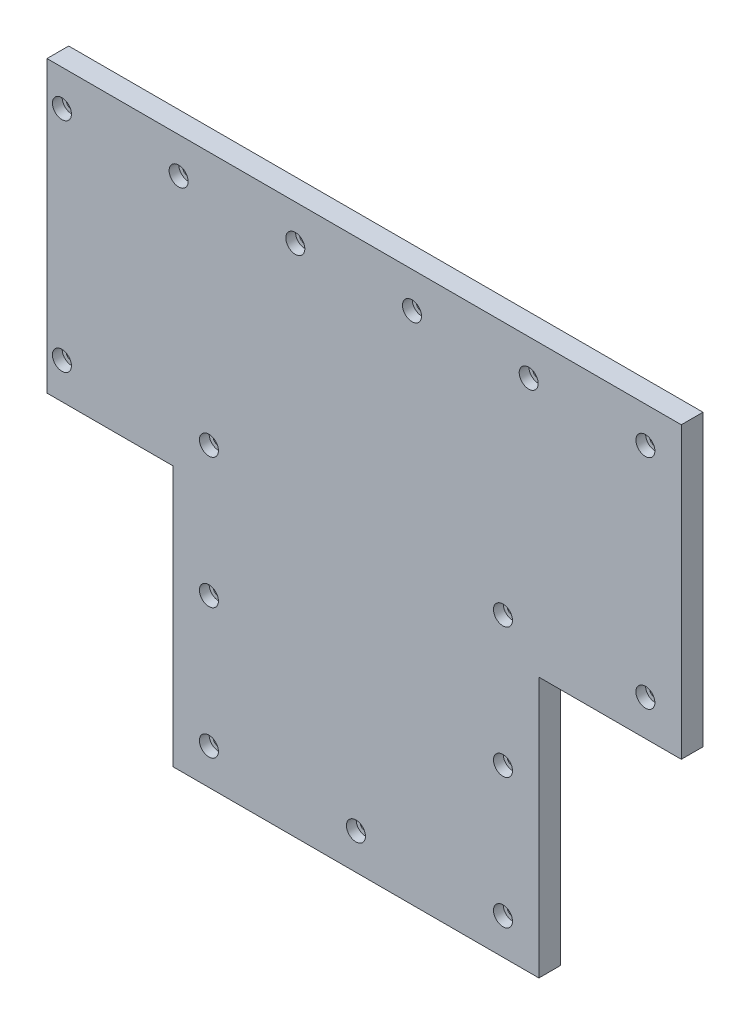
SolidWorks part; units mm, degrees
ref_plane "Front Plane" through (0, 0, 0) normal (0, 0, 1) x (1, 0, 0)
ref_plane "Top Plane" through (0, 0, 0) normal (0, 1, 0) x (1, 0, 0)
ref_plane "Right Plane" through (0, 0, 0) normal (1, 0, 0) x (0, 0, -1)
sketch "Outline" plane through (0, 0, 0) normal (0, 0, 1) x (1, 0, 0)
  line L0 (78.4332, -3.5355) -> (81.9688, 0)
  line L1 (0, 0) -> (180, 0)
  line L2 (0, 0) -> (0, -53.7401)
  line L3 (0, -53.7401) -> (180, -53.7401)
  line L4 (180, 0) -> (180, -53.7401)
  line L9 (81.9688, 0) -> (132.1734, -50.2046)
  line L10 (132.1734, -50.2046) -> (128.6378, -53.7401)
  line L11 (128.6378, -53.7401) -> (78.4332, -3.5355)
  line L12 (72.0693, 0) -> (68.5337, -3.5355)
  line L13 (68.5337, -3.5355) -> (118.7383, -53.7401)
  line L14 (118.7383, -53.7401) -> (122.2739, -50.2046)
  line L15 (122.2739, -50.2046) -> (72.0693, 0)
  line L16 (0, 10.6299) -> (0, -64.3701) construction
  line L17 (73.4835, -0.7071) -> (126.5165, -53.7401) construction
  line L18 (126.5165, -53.7401) -> (127.2236, -53.033) construction
  line L19 (127.2236, -53.033) -> (74.1906, 0) construction
  line L20 (74.1906, 0) -> (73.4835, -0.7071) construction
  line L21 (78.0797, -3.8891) -> (78.4332, -3.5355) construction
  line L22 (77.3726, -4.5962) -> (77.019, -4.9497) construction
  line L23 (100, -27.2236) -> (100, -53.7401) construction
  line L24 (62.3536, -53.7401) -> (138.3536, -53.7401)
  line L25 (62.3536, -53.7401) -> (62.3536, -129.9401)
  line L26 (62.3536, -129.9401) -> (138.3536, -129.9401)
  line L27 (138.3536, -53.7401) -> (138.3536, -129.9401)
  line L28 (62.3536, -53.7401) -> (74.1906, -53.7401)
  line L29 (62.3536, -53.7401) -> (62.3536, -55.7401)
  line L30 (62.3536, -55.7401) -> (74.1906, -55.7401)
  line L31 (74.1906, -53.7401) -> (74.1906, -55.7401)
  line L32 (138.3536, -53.7401) -> (126.5165, -53.7401)
  line L33 (138.3536, -53.7401) -> (138.3536, -55.7401)
  line L34 (138.3536, -55.7401) -> (126.5165, -55.7401)
  line L35 (126.5165, -53.7401) -> (126.5165, -55.7401)
  line L36 (62.3536, -57.9901) -> (74.1906, -57.9901)
  line L37 (62.3536, -57.9901) -> (62.3536, -59.9901)
  line L38 (62.3536, -59.9901) -> (74.1906, -59.9901)
  line L39 (74.1906, -57.9901) -> (74.1906, -59.9901)
  line L40 (138.3536, -57.9901) -> (126.5165, -57.9901)
  line L41 (138.3536, -57.9901) -> (138.3536, -59.9901)
  line L42 (138.3536, -59.9901) -> (126.5165, -59.9901)
  line L43 (126.5165, -57.9901) -> (126.5165, -59.9901)
  line L48 (137.8536, -55.7401) -> (137.8536, -56.2401) construction
  line L49 (62.8536, -56.2401) -> (137.8536, -56.2401) construction
  line L50 (62.8536, -56.2401) -> (62.8536, -57.4901) construction
  line L51 (62.8536, -57.4901) -> (137.8536, -57.4901) construction
  line L52 (137.8536, -56.2401) -> (137.8536, -57.4901) construction
  line L53 (137.8536, -57.4901) -> (137.8536, -57.9901) construction
  line L54 (137.8536, -56.2401) -> (138.3536, -56.2401) construction
  line L55 (62.8536, -56.2401) -> (62.3536, -56.2401) construction
  line L56 (0, 23.1299) -> (0, -76.8701) construction
  line L57 (10, 10) -> (190, 10)
  line L58 (0, 28.1299) -> (10, 28.1299)
  line L59 (0, 28.1299) -> (0, 0)
  line L60 (0, 0) -> (10, 0)
  line L61 (10, 28.1299) -> (10, 0)
  line L62 (0, -53.7401) -> (10, -53.7401)
  line L63 (0, -53.7401) -> (0, -81.8701)
  line L64 (0, -81.8701) -> (10, -81.8701)
  line L65 (10, -53.7401) -> (10, -81.8701)
  line L66 (190, 10) -> (190, -63.7401)
  line L67 (190, -63.7401) -> (148.3536, -63.7401)
  line L68 (148.3536, -63.7401) -> (148.3536, -139.9401)
  line L69 (148.3536, -139.9401) -> (52.3536, -139.9401)
  line L70 (52.3536, -139.9401) -> (52.3536, -63.7401)
  line L71 (52.3536, -63.7401) -> (10, -63.7401)
  line L72 (180, 0) -> (180, 10) construction
  line L73 (180, 0) -> (190, 0) construction
  line L74 (148.3536, -63.7401) -> (148.3536, -53.7401) construction
  line L75 (138.3536, -129.9401) -> (148.3536, -129.9401) construction
  line L76 (62.3536, -129.9401) -> (62.3536, -139.9401) construction
  line L77 (62.3536, -129.9401) -> (52.3536, -129.9401) construction
  line L78 (52.3536, -63.7401) -> (52.3536, -53.7401) construction
  line L79 (68.5337, -3.5355) -> (68.5337, 0)
  line L80 (126.5165, -53.7401) -> (127.5772, -52.6795)
  line L81 (10, 0) -> (10, -53.7401)
  line L82 (10, 5) -> (190, 5) construction
  line L83 (185, 10) -> (185, -63.7401) construction
  line L84 (190, -58.7401) -> (138.3536, -58.7401) construction
  line L85 (10, -58.7401) -> (62.3536, -58.7401) construction
  line L86 (57.3536, -53.7401) -> (57.3536, -139.9401) construction
  line L87 (52.3536, -134.9401) -> (148.3536, -134.9401) construction
  line L88 (143.3536, -53.7401) -> (143.3536, -139.9401) construction
  line L89 (10, 10) -> (0, 10)
  line L90 (190, -11.6201) -> (200, -11.6201) construction
  line L91 (190, -11.6201) -> (190, -42.1201) construction
  line L92 (190, -42.1201) -> (200, -42.1201) construction
  line L93 (200, -11.6201) -> (200, -42.1201) construction
  line L94 (10, -63.7401) -> (0, -63.7401)
  point P18 (0, -26.8701)
  point P51 (0, -26.8701)
  point P52 (0, -26.8701)
  point P80 (180, 5)
  point P83 (185, 0)
  point P85 (200, -26.8701)
  point P86 (190, -26.8701)
  point P94 (148.3536, -58.7401)
  point P103 (57.3536, -129.9401)
  point P104 (143.3536, -129.9401)
  point P105 (62.3536, -134.9401)
  dimension "D23" = 10
  dimension "D24" = 30.5
  dimension "D1" = 5
  dimension "D2" = 45
  dimension "D3" = 1
  dimension "D4" = 75
  dimension "D5" = 200
  dimension "D6" = 53.7401
  dimension "D7" = 0.5
  dimension "D8" = 75
  dimension "D9" = 1.25
  dimension "D10" = 0.5
  dimension "D11" = 76
  dimension "D12" = 52.3259
  dimension "D13" = 0.5
  dimension "D14" = 2
  dimension "D15" = 100
  dimension "D16" = 76.2
  dimension "D17" = 75
  dimension "D18" = 100
  dimension "D19" = 10
  dimension "D20" = 5
  dimension "D21" = 10
  dimension "D22" = 18.1299
sketch "Hole Locations" plane through (0, 0, 0) normal (0, 0, 1) x (1, 0, 0)
  line L8 (10, 5) -> (190, 5) construction
  line L9 (10, 28.1299) -> (10, 0) construction
  line L10 (10, -58.7401) -> (62.3536, -58.7401) construction
  line L11 (57.3536, -53.7401) -> (57.3536, -139.9401) construction
  line L12 (143.3536, -53.7401) -> (143.3536, -139.9401) construction
  line L13 (52.3536, -134.9401) -> (148.3536, -134.9401) construction
  line L14 (190, -58.7401) -> (138.3536, -58.7401) construction
  line L15 (185, 10) -> (185, -63.7401) construction
  circle A0 centre (14.3688, 5) radius 1.9431
  circle A1 centre (14.3688, 5) radius 4.3688 construction
  circle A2 centre (48.495, 5) radius 1.9431
  circle A3 centre (48.495, 5) radius 4.3688 construction
  circle A4 centre (82.6213, 5) radius 1.9431
  circle A5 centre (82.6213, 5) radius 4.3688 construction
  circle A6 centre (116.7475, 5) radius 1.9431
  circle A7 centre (116.7475, 5) radius 4.3688 construction
  circle A8 centre (150.8738, 5) radius 1.9431
  circle A9 centre (150.8738, 5) radius 4.3688 construction
  circle A10 centre (185, 5) radius 1.9431
  circle A11 centre (185, 5) radius 4.3688 construction
  circle A12 centre (14.3688, -58.7401) radius 1.9431
  circle A13 centre (14.3688, -58.7401) radius 4.3688 construction
  circle A14 centre (57.3536, -58.7401) radius 1.9431
  circle A15 centre (57.3536, -58.7401) radius 4.3688 construction
  circle A16 centre (185, -58.7401) radius 1.9431
  circle A17 centre (185, -58.7401) radius 4.3688 construction
  circle A18 centre (143.3536, -58.7401) radius 1.9431
  circle A19 centre (143.3536, -58.7401) radius 4.3688 construction
  circle A20 centre (57.3536, -134.9401) radius 1.9431
  circle A21 centre (57.3536, -134.9401) radius 4.3688 construction
  circle A22 centre (143.3536, -134.9401) radius 1.9431
  circle A23 centre (143.3536, -134.9401) radius 4.3688 construction
  circle A24 centre (57.3536, -96.8401) radius 1.9431
  circle A25 centre (57.3536, -96.8401) radius 4.3688 construction
  circle A26 centre (143.3536, -96.8401) radius 1.9431
  circle A27 centre (143.3536, -96.8401) radius 4.3688 construction
  circle A28 centre (100.3536, -134.9401) radius 1.9431
  circle A29 centre (100.3536, -134.9401) radius 4.3688 construction
  point P5 (15.9366, 5)
  point P25 (15.8274, -58.7401)
  point P27 (14.3688, -71.4228)
  point P31 (54.1459, -58.7401)
  point P35 (206.7106, -60.7454)
  point P39 (143.3536, -58.7401)
  point P42 (57.3536, -58.7401)
  point P43 (49.9418, -58.7401)
  point P44 (143.3536, -58.7401)
  point P45 (185, -58.7401)
  point P48 (57.9105, -58.7401)
  point P49 (0, 0)
  point P50 (0, 0)
  point P51 (22.1879, -58.7401)
  point P55 (42.4662, -130.2988)
  point P59 (162.7145, -130.2988)
  point P66 (158.6209, -94.4802)
  point P67 (33.7673, -90.6425)
  point P68 (57.3536, -134.9401)
  point P69 (0, 0)
  point P71 (143.3536, -134.9401)
  point P72 (0, 0)
  point P76 (0, 0)
  point P77 (100.3536, -134.9401)
  point P79 (57.3536, -134.9401)
  point P82 (143.3536, -134.9401)
  point P83 (0, 0)
  point P84 (0, 0)
  point P85 (0, 0)
  point P88 (185, -58.7401)
  point P91 (0, 0)
  point P92 (0, 0)
  point P93 (0, 0)
  point P94 (0, 0)
  point P95 (0, 0)
  point P96 (0, 0)
  point P97 (0, 0)
  point P98 (0, 0)
  dimension "D1" = 3.8862
  dimension "D2" = 8.7376
  dimension "D4" = 34.1262
  dimension "D3" = 6
extrude "Boss-Extrude1" add sketch "Outline" along normal blind 6.35 contours L71 L70 L69 L68 L67 L66 L57 L61 L1 L4 L3 L27 L26 L25 L65 | L43 L40 L27 L34 L35 L3 L24 L31 L30 L25 L36 L39 L38 L26 L42 | L31 L3 L25 L30 | L39 L36 L25 L38 | L24 L35 L34 L27 L3 | L40 L43 L42 L27 | L1 L81 L3 L24 L13 L79 | L3 L80 L11 L0 L1 L15 L14 | L14 L15 L12 L13 | L11 L10 L9 L0 | L9 L10 L3 L4 L1 | L80 L24 L11 | L79 L12 L1 region at (100.1794, -26.7004, 0) region at (105.3033, -26.8701, 0) region at (77.019, 2.3427, 0) region at (142.694, -23.5828, 0) region at (127.5772, -53.3866, 0) region at (69.7123, -1.1785, 0) region at (95.4038, -26.8701, 0) region at (132.435, -54.7401, 0) region at (100.3536, -92.4215, 0) region at (52.4252, -29.7691, 0) region at (68.2721, -54.7401, 0) region at (132.435, -58.9901, 0) region at (68.2721, -58.9901, 0)
hole_wizard "CBORE for #4 Socket Head Cap Screw1" positions "3DSketch1" profile "Sketch7" counterbore size "#4" standard "ANSI Inch" end condition through all
sketch3d "3DSketch1"
  point P0 (14.3688, 5, 6.35)
  point P2 (14.3688, -58.7401, 6.35)
  point P4 (57.3536, -58.7401, 6.35)
  point P6 (48.495, 5, 6.35)
  point P8 (82.6213, 5, 6.35)
  point P10 (116.7475, 5, 6.35)
  point P12 (150.8738, 5, 6.35)
  point P14 (143.3536, -58.7401, 6.35)
  point P16 (143.3536, -96.8401, 6.35)
  point P18 (57.3536, -134.9401, 6.35)
  point P20 (57.3536, -96.8401, 6.35)
  point P22 (185, -58.7401, 6.35)
  point P24 (185, 5, 6.35)
  point P47 (100.3536, -134.9401, 6.35)
  point P51 (143.3536, -134.9401, 6.35)
sketch "Sketch7" plane through (14.3688, 5, 6.35) normal (1, 0, 0) x (0, -1, 0)
  line L0 (0, 0) -> (0, 6.35)
  line L1 (0, 6.35) -> (1.6319, 6.35)
  line L3 (1.6319, 6.35) -> (1.6319, 2.8448)
  line L4 (1.6319, 2.8448) -> (2.7788, 2.8448)
  line L5 (2.7788, 2.8448) -> (2.7788, 0)
  line L7 (2.7788, 0) -> (0, 0)
  line L11 (0, -6.35) -> (0, 107.95) construction
  dimension "Thru Hole Dia." = 3.2639
  dimension "Thru Hole Depth" = 6.35
  dimension "C'Bore Dia." = 5.5575
  dimension "C'Bore Depth" = 2.8448
extrude "Boss-Extrude2" add sketch "Outline<10>" against normal blind 2 contours L11 L10 L9 L0 | L14 L15 L12 L13 region at (105.3033, -26.8701, 0) region at (95.4038, -26.8701, 0)
sketch "Outline<10>" plane through (0, 0, 0) normal (0, 0, 1) x (1, 0, 0) same geometry as "Outline"
sketch "Sketch8" plane through (0, 0, 0) normal (0, 0, 1) x (1, 0, 0)
  line L0 (0, 10) -> (0, 13.5)
  line L1 (0, 13.5) -> (193.5, 13.5)
  line L2 (193.5, 13.5) -> (193.5, -67.2401)
  line L3 (193.5, -67.2401) -> (151.8536, -67.2401)
  line L4 (151.8536, -67.2401) -> (151.8536, -143.4401)
  line L5 (151.8536, -143.4401) -> (48.8536, -143.4401)
  line L6 (48.8536, -143.4401) -> (48.8536, -67.2401)
  line L7 (48.8536, -67.2401) -> (0, -67.2401)
  line L8 (0, -67.2401) -> (0, -63.7401)
  line L9 (190, 10) -> (193.5, 10) construction
  line L10 (190, 10) -> (190, 13.5) construction
  line L11 (190, -63.7401) -> (193.5, -63.7401) construction
  line L12 (190, -63.7401) -> (190, -67.2401) construction
  line L13 (151.8536, -67.2401) -> (151.8536, -63.7401) construction
  line L14 (190, -63.7401) -> (148.3536, -63.7401) construction
  line L15 (151.8536, -67.2401) -> (148.3536, -67.2401) construction
  line L16 (148.3536, -63.7401) -> (148.3536, -139.9401) construction
  line L17 (148.3536, -139.9401) -> (151.8536, -139.9401) construction
  line L18 (148.3536, -139.9401) -> (148.3536, -143.4401) construction
  line L19 (52.3536, -139.9401) -> (52.3536, -143.4401) construction
  line L20 (52.3536, -139.9401) -> (48.8536, -139.9401) construction
  line L21 (48.8536, -67.2401) -> (52.3536, -67.2401) construction
  line L22 (52.3536, -139.9401) -> (52.3536, -63.7401) construction
  line L23 (48.8536, -67.2401) -> (48.8536, -63.7401) construction
  line L25 (0, 13.5) -> (0, 15.5)
  line L26 (0, 15.5) -> (195.5, 15.5)
  line L27 (195.5, 15.5) -> (195.5, -69.2401)
  line L28 (195.5, -69.2401) -> (153.8536, -69.2401)
  line L29 (153.8536, -69.2401) -> (153.8536, -145.4401)
  line L30 (153.8536, -145.4401) -> (46.8536, -145.4401)
  line L31 (46.8536, -145.4401) -> (46.8536, -69.2401)
  line L32 (46.8536, -69.2401) -> (0, -69.2401)
  line L33 (0, -69.2401) -> (0, -67.2401)
  line L34 (46.8536, -69.2401) -> (48.8536, -69.2401) construction
  line L35 (46.8536, -69.2401) -> (46.8536, -67.2401) construction
  line L36 (48.8536, -143.4401) -> (46.8536, -143.4401) construction
  line L37 (48.8536, -143.4401) -> (48.8536, -145.4401) construction
  line L38 (151.8536, -143.4401) -> (153.8536, -143.4401) construction
  line L39 (151.8536, -143.4401) -> (151.8536, -145.4401) construction
  line L40 (153.8536, -69.2401) -> (153.8536, -67.2401) construction
  line L41 (153.8536, -69.2401) -> (151.8536, -69.2401) construction
  line L42 (193.5, -67.2401) -> (195.5, -67.2401) construction
  line L43 (193.5, -67.2401) -> (193.5, -69.2401) construction
  line L44 (193.5, 13.5) -> (195.5, 13.5) construction
  line L45 (193.5, 13.5) -> (193.5, 15.5) construction
  line L46 (0, -63.7401) -> (0, -69.2401)
  line L47 (0, -63.7401) -> (52.3536, -63.7401)
  line L48 (52.3536, -63.7401) -> (52.3536, -139.9401)
  line L49 (52.3536, -139.9401) -> (148.3536, -139.9401)
  line L50 (148.3536, -139.9401) -> (148.3536, -63.7401)
  line L51 (148.3536, -63.7401) -> (190, -63.7401)
  line L52 (190, -63.7401) -> (190, 10)
  line L53 (190, 10) -> (0, 10)
  line L54 (0, 9.5) -> (189.5, 9.5)
  line L56 (189.5, 9.5) -> (189.5, -63.2401)
  line L57 (189.5, -63.2401) -> (147.8536, -63.2401)
  line L58 (147.8536, -63.2401) -> (147.8536, -139.4401)
  line L59 (147.8536, -139.4401) -> (52.8536, -139.4401)
  line L60 (52.8536, -139.4401) -> (52.8536, -63.2401)
  line L61 (52.8536, -63.2401) -> (0, -63.2401)
  line L62 (189.5, 9.5) -> (189.5, 10) construction
  line L63 (189.5, 9.5) -> (190, 9.5) construction
  line L64 (189.5, -63.2401) -> (190, -63.2401) construction
  line L65 (189.5, -63.2401) -> (189.5, -63.7401) construction
  line L66 (148.3536, -63.7401) -> (148.3536, -63.2401) construction
  line L67 (148.3536, -63.7401) -> (147.8536, -63.7401) construction
  line L68 (147.8536, -139.4401) -> (148.3536, -139.4401) construction
  line L69 (147.8536, -139.4401) -> (147.8536, -139.9401) construction
  line L70 (52.8536, -139.4401) -> (52.8536, -139.9401) construction
  line L71 (52.8536, -139.4401) -> (52.3536, -139.4401) construction
  line L72 (52.3536, -63.7401) -> (52.3536, -63.2401) construction
  line L73 (52.3536, -63.7401) -> (52.8536, -63.7401) construction
  line L74 (0, 9.5) -> (0, 10)
  line L75 (0, -63.2401) -> (0, -63.7401)
  line L76 (10, 10) -> (10, 15.5)
  line L77 (10, -63.7401) -> (10, -69.2401)
  line L78 (52.3536, -63.7401) -> (10, -63.7401) construction
  line L79 (10, 10) -> (190, 10) construction
  point P40 (0, 0)
  point P41 (0, 0)
  point P67 (0, 0)
  point P68 (0, 0)
  point P93 (0, 0)
  point P94 (0, 0)
  point P95 (0, 0)
  point P96 (0, 0)
  point P97 (52.8536, -62.5066)
  point P98 (0, 0)
  point P101 (0, 0)
  point P102 (0, 0)
  point P103 (190, 10)
  dimension "D1" = 3.5
  dimension "D2" = 2
  dimension "D3" = 0.5
extrude "Boss-Extrude3" add sketch "Sketch8" along normal up to surface (6.35 mm away) contours L53 L52 L51 L50 L49 L48 L47 L8 L7 L6 L5 L4 L3 L2 L1 L0 | L33 L32 L31 L30 L29 L28 L27 L26 L25 L1 L2 L3 L4 L5 L6 L7 region at (12.4146, 11.75, 0) region at (12.4558, 14.5, 0) up to face at (17.1476, 5, 6.35)
extrude "Cut-Extrude1" cut sketch "Sketch8<5>" along normal blind 3 contours L53 L52 L51 L50 L49 L48 L47 L8 L7 L6 L5 L4 L3 L2 L1 L0 | L61 L75 L47 L48 L49 L50 L51 L52 L53 L74 L54 L56 L57 L58 L59 L60 region at (5, 9.758, 0) region at (12.4146, 11.75, 0)
sketch "Sketch8<5>" plane through (0, 0, 0) normal (0, 0, 1) x (1, 0, 0) same geometry as "Sketch8"
